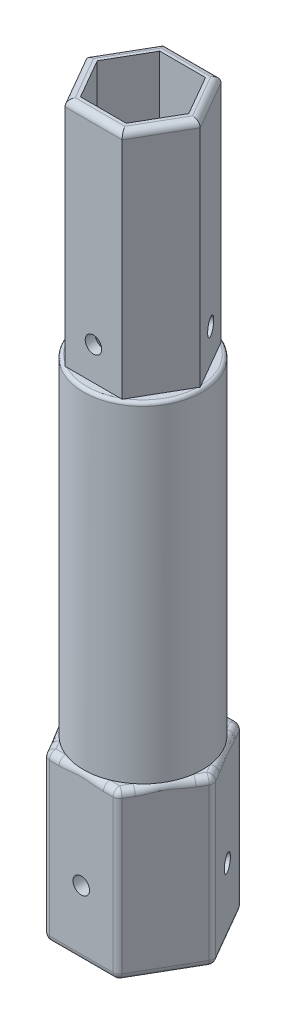
SolidWorks part; units mm, degrees
ref_plane "Front Plane" through (0, 0, 0) normal (0, 0, 1) x (1, 0, 0)
ref_plane "Top Plane" through (0, 0, 0) normal (0, 1, 0) x (1, 0, 0)
ref_plane "Right Plane" through (0, 0, 0) normal (1, 0, 0) x (0, 0, -1)
sketch "Sketch1" plane through (0, 0, 0) normal (0, 1, 0) x (1, 0, 0)
  line L1 (10.7965, 0) -> (5.3982, 9.35)
  line L2 (5.3982, 9.35) -> (-5.3982, 9.35)
  line L3 (-5.3982, 9.35) -> (-10.7965, 0)
  line L4 (-10.7965, 0) -> (-5.3982, -9.35)
  line L5 (-5.3982, -9.35) -> (5.3982, -9.35)
  line L6 (5.3982, -9.35) -> (10.7965, 0)
  circle A0 centre (0, 0) radius 9.35 construction
  dimension "D1" = 18.7
extrude "Base" add sketch "Sketch1" along normal blind 25 contours L6 L1 L2 L3 L4 L5
sketch "Sketch2" plane through (0, 25, 0) normal (0, 1, 0) x (1, 0, 0)
  circle A0 centre (0, 0) radius 9
  dimension "D1" = 18
extrude "Shaft" add sketch "Sketch2" along normal blind 50
sketch "Sketch3" plane through (0, 75, 0) normal (0, 1, 0) x (1, 0, 0)
  line L1 (8.6603, 0) -> (4.3301, 7.5)
  line L2 (4.3301, 7.5) -> (-4.3301, 7.5)
  line L3 (-4.3301, 7.5) -> (-8.6603, 0)
  line L4 (-8.6603, 0) -> (-4.3301, -7.5)
  line L5 (-4.3301, -7.5) -> (4.3301, -7.5)
  line L6 (4.3301, -7.5) -> (8.6603, 0)
  circle A0 centre (0, 0) radius 7.5 construction
  point P10 (0, 0)
  dimension "D1" = 15
extrude "MicMount" add sketch "Sketch3" along normal blind 35
sketch "Sketch4" plane through (0, 0, 0) normal (0, -1, 0) x (1, 0, 0)
  line L0 (5.3982, -9.35) -> (-5.3982, -9.35) construction
  line L1 (-3.6662, -6.35) -> (3.6662, -6.35)
  line L2 (3.6662, -6.35) -> (7.3323, 0)
  line L3 (7.3323, 0) -> (3.6662, 6.35)
  line L4 (3.6662, 6.35) -> (-3.6662, 6.35)
  line L5 (-3.6662, 6.35) -> (-7.3323, 0)
  line L6 (-7.3323, 0) -> (-3.6662, -6.35)
  circle A0 centre (0, 0) radius 6.35 construction
  dimension "D1" = 12.7
extrude "Cut-Extrude1" cut sketch "Sketch4" against normal up to surface (75 mm away) up to face at (0, 75, 0)
sketch "ScrewHoleLoc" plane through (6.4952, 0, -3.75) normal (0.866, 0, -0.5) x (-0.5, 0, -0.866)
  line L0 (0, 48.1931) -> (0, 111.8069) construction
  line L1 (9, 75) -> (-9, 75) construction
  point P0 (0, 80)
hole_wizard "ScrewHole" positions "3DSketch1" profile "Sketch6" hole size "Ø2.5" standard "ANSI Metric"
sketch3d "3DSketch1"
  point P0 (6.4952, 80, -3.75)
sketch "Sketch6" plane through (6.4952, 80, -3.75) normal (0, 1, 0) x (-0.5, 0, -0.866)
  line L0 (0, 0) -> (0, 2.7511)
  line L1 (0, 2.7511) -> (1.25, 2)
  line L2 (1.25, 2) -> (1.25, 0)
  line L5 (1.25, 0) -> (0, 0)
  line L10 (0, 2.7511) -> (-1.25, 2) construction
  line L11 (0, -6.35) -> (0, 107.95) construction
  dimension "Hole Dia." = 2.5
  dimension "Hole Depth" = 2
  dimension "Drill Angle" = 118
ref_axis "Axis1" through (0, 54.4687, 0) along (0, 1, 0)
pattern_circular "ScrewHoleS" count 3 over 360 about axis through (0, 54.4687, 0) along (0, 1, 0) of "ScrewHole"
sketch "Sketch7" plane through (0, 110, 0) normal (0, 1, 0) x (1, 0, 0)
  line L12 (3.4641, -6) -> (6.9282, 0)
  line L13 (6.9282, 0) -> (3.4641, 6)
  line L14 (3.4641, 6) -> (-3.4641, 6)
  line L15 (-3.4641, 6) -> (-6.9282, 0)
  line L16 (-6.9282, 0) -> (-3.4641, -6)
  line L17 (-3.4641, -6) -> (3.4641, -6)
  line L18 (3.4641, -6) -> (6.9282, 0)
  line L19 (6.9282, 0) -> (3.4641, 6)
  line L20 (3.4641, 6) -> (-3.4641, 6)
  line L21 (-3.4641, 6) -> (-6.9282, 0)
  line L22 (-6.9282, 0) -> (-3.4641, -6)
  line L23 (-3.4641, -6) -> (3.4641, -6)
  dimension "D1" = 1.5
extrude "Cut-Extrude2" cut sketch "Sketch7" against normal up to next
sketch "ShaftMountLoc" plane through (-8.0973, 0, -4.675) normal (-0.866, 0, -0.5) x (-0.5, 0, 0.866)
  line L0 (0, 10) -> (0, 7.4851) construction
  line L1 (5.3982, 25) -> (5.3982, 0) construction
  line L2 (-5.3982, 25) -> (-5.3982, 0) construction
  line L3 (-5.3982, 0) -> (5.3982, 0) construction
  point P0 (0, 10)
  dimension "D1" = 10
hole_wizard "ShaftMount" positions "3DSketch3" profile "Sketch10" hole size "Ø2.5" standard "ANSI Metric" end condition up to next
sketch3d "3DSketch3"
  point P0 (-8.0973, 10, -4.675)
sketch "Sketch10" plane through (-8.0973, 10, -4.675) normal (0, 1, 0) x (-0.5, 0, 0.866)
  line L0 (0, 0) -> (0, 18.7)
  line L1 (0, 18.7) -> (1.25, 18.7)
  line L2 (1.25, 18.7) -> (1.25, 0)
  line L5 (1.25, 0) -> (0, 0)
  line L11 (0, -6.35) -> (0, 107.95) construction
  dimension "Thru Hole Dia." = 2.5
  dimension "Thru Hole Depth" = 18.7
pattern_circular "CirPattern2" count 3 over 360 about axis through (0, 54.4687, 0) along (0, 1, 0) of "ShaftMount"
fillet "Fillet2" radius 1 24 edges at (8.0973, 0, -4.675) (-8.0973, 0, -4.675) (0, 0, 9.35) (5.4993, 0, 3.175) (0, 0, 6.35) (-5.4993, 0, 3.175) (-5.4993, 0, -3.175) (0, 0, -6.35) (5.4993, 0, -3.175) (5.3982, 12.5, 9.35) (8.0973, 25, 4.675) (10.7965, 12.5, 0) (8.0973, 0, 4.675) (-10.7965, 12.5, 0) (-8.0973, 25, 4.675) (-5.3982, 12.5, 9.35) (-8.0973, 0, 4.675) (5.3982, 12.5, -9.35) (0, 25, -9.35) (-5.3982, 12.5, -9.35) (0, 0, -9.35) (-8.0973, 25, -4.675) (8.0973, 25, -4.675) (0, 25, 9.35)
fillet "Fillet5" radius 1 6 edges at (6.4952, 110, -3.75) (6.4952, 110, 3.75) (0, 110, 7.5) (-6.4952, 110, 3.75) (-6.4952, 110, -3.75) (0, 110, -7.5)
fillet "Fillet8" radius 0.5 1 edges at (0, 75, 9)
equation "\"D1@Sketch3\"= \"SHAFT_MOUNTOD\""
equation "\"D1@Base\"=25"
equation "\"D1@Shaft\"=50"
equation "\"D1@Sketch2\"= \"SHAFT_D\""
equation "\"D1@Sketch4\" = \"SHAFT_BASEID\""
equation "\"D1@MicMount\" = \"SHAFT_MOUNTH\""
equation "\"D1@ShaftMountLoc\"= \"SHAFT_BASEHOLEH\""
equation "\"D1@Sketch1\" = \"SHAFT_BASEOD\""
equation "\"SHAFT_MOUNTOD\" = \"BMOUNT_HEXID\""
equation "\"CB_W\" = 5"
equation "\"CW_DEPTH\" = 1"
equation "\"PIN_SPACING\" = 2.54"
equation "\"PIN_D\" = 1"
equation "\"PCB_THICK\" = 1.5"
equation "\"TAP_HOLE\" = 2.5"
equation "\"SCREW_HOLE\" = 3"
equation "\"SLIPRING_D\" = 12.4"
equation "\"SLIPRING_MOUNTOD\" = 15"
equation "\"SLIPRING_MOUNTTHICK\" = 8"
equation "\"SLIPRING_MOUNT_LEGH\" = 12"
equation "\"PITCH_D\"= 44.45"
equation "\"HEX_D\"= 12.7"
equation "\"BODY_Y\"= 70"
equation "\"BODY_X\"= 60"
equation "\"BODY_Z\"= 120"
equation "\"BODY_THICK\"= 3"
equation "\"BODY_TOPTHICK\"= 4"
equation "\"STAND_R\" = 3"
equation "\"STAND_ZOFF\" = 10"
equation "\"STAND_XOFF\" = 5"
equation "\"MOTOR_ZOFF\" = 25"
equation "\"MOTOR_MOUNTANGLE\" = 120"
equation "\"MOTOR_D\"= 28"
equation "\"MOTOR_H\"= 19"
equation "\"MOTOR_HOLEDIST\"= 35"
equation "\"MOTOR_SHAFTOFF\" = 8"
equation "\"DRVR_Y\" = 31"
equation "\"DRVR_Z\" = 27"
equation "\"DRVR_YOFF\" = 15"
equation "\"DRVR_ARDOFF\" = 10"
equation "\"BEARING_OD\" = 28.575"
equation "\"BEARING_ID\" = 12.7"
equation "\"BEARING_THICK\" = 7.925"
equation "\"BEARING_FLANGE_D\" = 31.242"
equation "\"BEARING_FLANGETHICK\" = 1.575"
equation "\"COLLAR_OD\" = 20.5"
equation "\"BMOUNT_X\" = 30"
equation "\"BMOUNT_HEXID\" = 15"
equation "\"BMOUNT_HEXTHICK\" = 2"
equation "\"BMOUNT_HEXH\" = 35"
equation "\"BMOUNT_HOLEX\" = 4*\"PIN_SPACING\""
equation "\"BMOUNT_HOLEZ\" = 4*\"PIN_SPACING\""
equation "\"BMOUNT_SCREWH\" = 5"
equation "\"MBOARD_MHOLEX\" = 10*\"PIN_SPACING\""
equation "\"MBOARD_MHOLEXOFF\" = 2*\"PIN_SPACING\""
equation "\"MBOARD_MHOLEZ\" = 9*\"PIN_SPACING\""
equation "\"MBOARD_POGOSPACING\" = 1*\"PIN_SPACING\""
equation "\"MBOARD_POGOX\" = 7*\"PIN_SPACING\""
equation "\"MBOARD_POGOXOFF\" = 1*\"PIN_SPACING\""
equation "\"MBOARD_POGOZ\" = 7*\"PIN_SPACING\""
equation "\"MBOARD_W\" = 28*\"PIN_SPACING\""
equation "\"SHAFT_BASEID\" = 12.7"
equation "\"SHAFT_BASEOD\" = \"SHAFT_BASEID\" + 2*3"
equation "\"SHAFT_D\" = 18"
equation "\"HEXSHAFT_D\" = 12.75"
equation "\"HEXSHAFT_FILLET\" = 2.5"
equation "\"D1@ScrewHoleLoc\"=\"BMOUNT_SCREWH\""
equation "\"SHAFT_BASEHOLEH\" = 10"
equation "\"SHAFT_MOUNTH\" = \"BMOUNT_HEXH\" "
equation "\"MBOARD_MDEPTH\"= 15"
equation "\"STAND_XOFF\"= 5"
